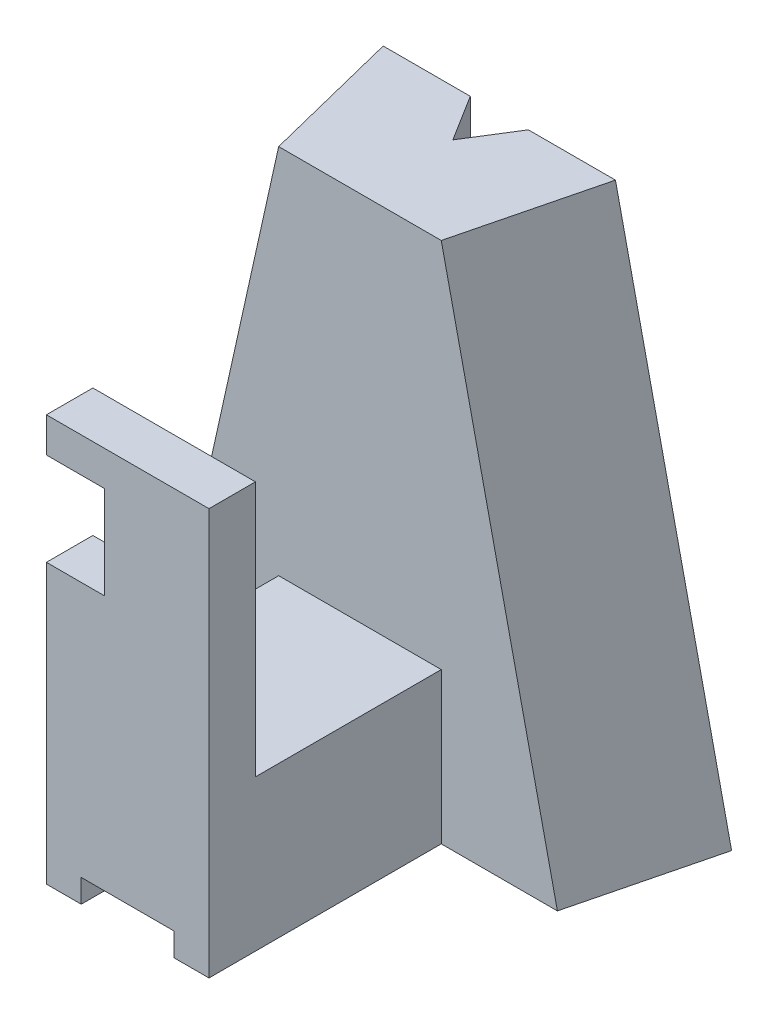
SolidWorks part; units mm, degrees
ref_plane "Спереди" through (0, 0, 0) normal (0, 0, 1) x (1, 0, 0)
ref_plane "Сверху" through (0, 0, 0) normal (0, 1, 0) x (1, 0, 0)
ref_plane "Справа" through (0, 0, 0) normal (1, 0, 0) x (0, 0, -1)
sketch "Эскиз1" plane through (0, 0, 0) normal (0, 0, 1) x (1, 0, 0)
  line L0 (0, 0) -> (0, 36.0228) construction
  line L1 (-10, 45) -> (10, 45)
  line L2 (10, 45) -> (20, 0)
  line L3 (20, 0) -> (-20, 0)
  line L4 (-10, 45) -> (-20, 0)
  point P8 (0, 45)
  dimension "D1" = 45
  dimension "D2" = 20
  dimension "D3" = 10
extrude "Бобышка-Вытянуть1" add sketch "Эскиз1" along normal blind 12
sketch "Эскиз2" plane through (0, 0, 0) normal (0, -1, 0) x (1, 0, 0)
  line L0 (-20, 0) -> (-20, 12)
  line L1 (-20, 12) -> (-20, 0) construction
  line L2 (-20, 12) -> (-17, 12)
  line L3 (-20, 12) -> (20, 12) construction
  line L4 (-17, 12) -> (-20, 0)
  dimension "D1" = 3
extrude "Вырез-Вытянуть1" cut sketch "Эскиз2" along direction (-0.2169, -0.9762, 0) on the side against the normal through all
sketch "Эскиз3" plane through (0, 0, 0) normal (0, -1, 0) x (1, 0, 0)
  line L0 (20, 0) -> (20, 12)
  line L1 (20, 12) -> (17, 12)
  line L2 (17, 12) -> (20, 0)
  dimension "D1" = 3
extrude "Вырез-Вытянуть2" cut sketch "Эскиз3" along direction (-0.2169, 0.9762, 0) on the side against the normal through all
sketch "Эскиз4" plane through (0, 45, 0) normal (0, 1, 0) x (1, 0, 0)
  line L0 (0, 0) -> (0, -12) construction
  line L1 (7, -12) -> (-7, -12) construction
  line L2 (0, 0) -> (-2.5, 0)
  line L3 (10, 0) -> (-10, 0) construction
  line L4 (-2.5, 0) -> (0, -4)
  line L5 (0, -4) -> (2.5, 0)
  line L6 (2.5, 0) -> (0, 0)
  dimension "D1" = 4
  dimension "D2" = 2.5
extrude "Вырез-Вытянуть3" cut sketch "Эскиз4" against normal through all
sketch "Эскиз5" plane through (0, 0, 0) normal (1, 0, 0) x (0, 0, -1)
  line L0 (-12, 0) -> (-32, 0)
  line L1 (-32, 0) -> (-32, 35)
  line L2 (-32, 35) -> (-28, 35)
  line L3 (-28, 35) -> (-28, 13)
  line L4 (-28, 13) -> (-12, 13)
  line L5 (-12, 45) -> (-12, 0) construction
  line L6 (-12, 13) -> (-12, 0)
  dimension "D1" = 20
  dimension "D2" = 4
  dimension "D3" = 35
  dimension "D4" = 13
extrude "Бобышка-Вытянуть2" add sketch "Эскиз5" along normal blind 7 and the other way blind 7
sketch "Эскиз6" plane through (0, 0, 32) normal (0, 0, 1) x (1, 0, 0)
  line L0 (0, 0) -> (0, 35) construction
  line L1 (-7, 35) -> (7, 35) construction
  line L2 (-7, 0) -> (7, 0) construction
  line L3 (-4, 2) -> (4, 2)
  line L4 (-4, 2) -> (-4, 0)
  line L5 (-4, 0) -> (4, 0)
  line L6 (4, 2) -> (4, 0)
  line L7 (-4, 2) -> (4, 0) construction
  line L8 (-4, 0) -> (4, 2) construction
  point P5 (0, 1)
  dimension "D1" = 8
  dimension "D2" = 2
extrude "Вырез-Вытянуть4" cut sketch "Эскиз6" against normal blind 5
sketch "Эскиз7" plane through (-7, 0, 0) normal (-1, 0, 0) x (0, 0, 1)
  line L0 (28, 13) -> (28, 35) construction
  line L1 (28, 32) -> (32, 32)
  line L2 (28, 32) -> (28, 24)
  line L3 (28, 24) -> (32, 24)
  line L4 (32, 32) -> (32, 24)
  line L5 (32, 35) -> (32, 0) construction
  line L6 (28, 35) -> (32, 35) construction
  dimension "D1" = 8
  dimension "D2" = 3
extrude "Вырез-Вытянуть5" cut sketch "Эскиз7" against normal blind 5
sketch "Эскиз8" plane through (-7, 0, 0) normal (1, 0, 0) x (0, 0, -1)
  line L0 (-12, 6.5) -> (-32, 6.5) construction
  line L1 (-12, 0) -> (-12, 13) construction
  line L2 (-32, 35) -> (-32, 0) construction
  line L3 (-28, 13) -> (-28, 35) construction
  line L4 (-23, 4) -> (-28, 4)
  line L5 (-23, 4) -> (-23, 9)
  line L6 (-23, 9) -> (-28, 9)
  line L7 (-28, 4) -> (-28, 9)
  line L8 (-23, 4) -> (-28, 9) construction
  line L9 (-23, 9) -> (-28, 4) construction
  point P6 (-25.5, 6.5)
  dimension "D1" = 5
  dimension "D2" = 5
extrude "Вырез-Вытянуть6" cut sketch "Эскиз8" along normal blind 2
